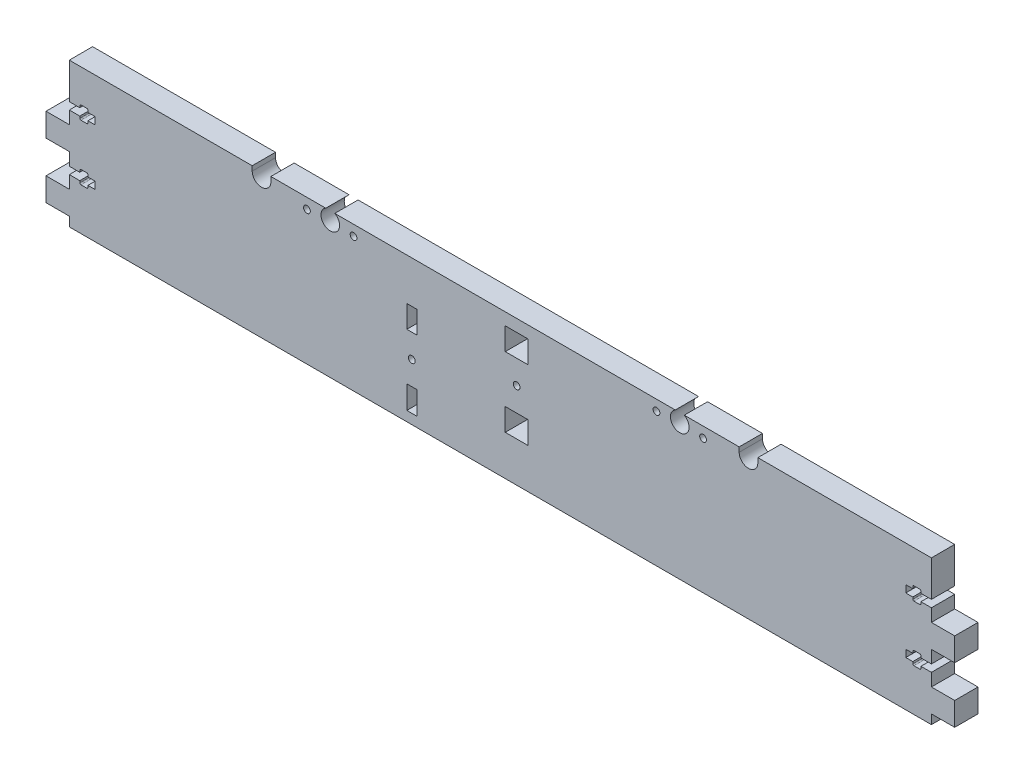
SolidWorks part; units mm, degrees
ref_plane "Front Plane" through (0, 0, 0) normal (0, 0, 1) x (1, 0, 0)
ref_plane "Top Plane" through (0, 0, 0) normal (0, 1, 0) x (1, 0, 0)
ref_plane "Right Plane" through (0, 0, 0) normal (1, 0, 0) x (0, 0, -1)
sketch "Sketch1" plane through (0, 0, 0) normal (0, 0, 1) x (1, 0, 0)
  line L0 (0, 0) -> (-185, 0)
  line L1 (-185, 0) -> (-185, -62) construction
  line L2 (0, -62) -> (-185, -62)
  line L3 (-185, -62) -> (-185, -58)
  line L4 (-185, -58) -> (-195, -58)
  line L5 (-195, -58) -> (-195, -48)
  line L6 (-195, -48) -> (-185, -48)
  line L7 (-185, -48) -> (-185, -34)
  line L8 (-185, -34) -> (-195, -34)
  line L9 (-195, -34) -> (-195, -24)
  line L10 (-195, -24) -> (-185, -24)
  line L11 (0, -62) -> (0, 0)
  line L12 (-185, -24) -> (-185, 0)
  line L13 (-195, -58) -> (-195, -24) construction
  line L14 (-195, -29) -> (-185, -29) construction
  line L15 (-195, -53) -> (-185, -53) construction
  dimension "D1" = 185
  dimension "D2" = 10
  dimension "D3" = 10
  dimension "D4" = 10
  dimension "D5" = 24
  dimension "D6" = 29
  dimension "D7" = 62
extrude "MainBody" add sketch "Sketch1" along normal blind 10
sketch "Sketch3" plane through (0, 0, 10) normal (0, 0, 1) x (1, 0, 0)
  line L0 (-185, -17) -> (-174, -17) construction
  line L1 (-185, 0) -> (-185, -24) construction
  line L2 (-185, -18.55) -> (-180.5, -18.55)
  line L3 (-180.5, -18.55) -> (-180.5, -19.35)
  line L4 (-180, -19.85) -> (-177.5, -19.85)
  line L5 (-177, -19.35) -> (-177, -18.55)
  line L6 (-177, -18.55) -> (-174, -18.55)
  line L7 (-174, -18.55) -> (-174, -15.45)
  line L8 (-180.5, -18.55) -> (-177, -18.55) construction
  line L9 (-195, -24) -> (-195, -34) construction
  line L10 (-180.5, -15.45) -> (-177, -15.45) construction
  line L11 (-177, -15.45) -> (-174, -15.45)
  line L12 (-177, -14.65) -> (-177, -15.45)
  line L13 (-180, -14.15) -> (-177.5, -14.15)
  line L14 (-180.5, -15.45) -> (-180.5, -14.65)
  line L15 (-185, -15.45) -> (-180.5, -15.45)
  line L16 (-185, -18.55) -> (-185, -15.45)
  line L17 (-185, -24) -> (-185, -34) construction
  line L19 (-195, -24) -> (-195, -34) construction
  line L20 (-195, -29) -> (-185, -29) construction
  line L21 (-180.5, -42.55) -> (-177, -42.55) construction
  line L22 (-180.5, -39.45) -> (-177, -39.45) construction
  line L23 (-185, -41) -> (-174, -41) construction
  line L24 (-185, -39.45) -> (-185, -42.55)
  line L25 (-185, -42.55) -> (-180.5, -42.55)
  line L26 (-180.5, -42.55) -> (-180.5, -43.35)
  line L27 (-180, -43.85) -> (-177.5, -43.85)
  line L28 (-177, -43.35) -> (-177, -42.55)
  line L29 (-177, -42.55) -> (-174, -42.55)
  line L30 (-174, -39.45) -> (-174, -42.55)
  line L31 (-177, -39.45) -> (-174, -39.45)
  line L32 (-177, -38.65) -> (-177, -39.45)
  line L33 (-180, -38.15) -> (-177.5, -38.15)
  line L34 (-180.5, -39.45) -> (-180.5, -38.65)
  line L35 (-185, -39.45) -> (-180.5, -39.45)
  line L36 (-180.5, -15.45) -> (-177, -15.45) construction
  arc A0 (-177.5, -19.85) -> (-177, -19.35) centre (-177.5, -19.35) ccw
  arc A1 (-180.5, -19.35) -> (-180, -19.85) centre (-180, -19.35) ccw
  arc A2 (-180.5, -14.65) -> (-180, -14.15) centre (-180, -14.65) cw
  arc A3 (-177.5, -14.15) -> (-177, -14.65) centre (-177.5, -14.65) cw
  arc A4 (-177.5, -43.85) -> (-177, -43.35) centre (-177.5, -43.35) ccw
  arc A5 (-180.5, -43.35) -> (-180, -43.85) centre (-180, -43.35) ccw
  arc A6 (-180.5, -38.65) -> (-180, -38.15) centre (-180, -38.65) cw
  arc A7 (-177.5, -38.15) -> (-177, -38.65) centre (-177.5, -38.65) cw
  point P6 (-195, -29)
  point P15 (-177, -19.85)
  point P18 (-180.5, -19.85)
  point P29 (-180.5, -14.15)
  point P30 (-177, -14.15)
  point P62 (-177, -43.85)
  point P63 (-180.5, -43.85)
  point P64 (-180.5, -38.15)
  point P65 (-177, -38.15)
  dimension "D2" = 8
  dimension "D7" = 0.5
  dimension "D1" = 11
  dimension "D3" = 1.55
  dimension "D4" = 2.85
  dimension "D5" = 12
  dimension "D6" = 3.5
extrude "ScrewCutouts" cut sketch "Sketch3" against normal through all
mirror "Mirror1" about plane through (0, 0, 0) normal (1, 0, 0) of "ScrewCutouts", "MainBody"
sketch "Sketch2" plane through (0, 0, 10) normal (0, 0, 1) x (1, 0, 0)
  line L0 (0, 0) -> (0, -62) construction
  line L1 (-185, -62) -> (185, -62) construction
  line L2 (2, 0) -> (2, -62) construction
  line L3 (185, 0) -> (-185, 0) construction
  line L4 (-63, -4.5) -> (-83, -4.5) construction
  line L5 (-73, -7.5) -> (-73, 0.5) construction
  line L6 (77, -7.5) -> (77, 0.5) construction
  line L7 (67, -4.5) -> (87, -4.5) construction
  circle A0 centre (-73, -3.5) radius 4
  circle A1 centre (-83, -4.5) radius 1.45
  circle A2 centre (-63, -4.5) radius 1.45
  circle A3 centre (67, -4.5) radius 1.45
  circle A4 centre (87, -4.5) radius 1.45
  circle A5 centre (77, -3.5) radius 4
  dimension "D1" = 2.9
  dimension "D2" = 8
  dimension "D4" = 3.5
  dimension "D5" = 75
  dimension "D6" = 2
  dimension "D3" = 10
  dimension "D7" = 1
extrude "RodCutouts" cut sketch "Sketch2" against normal through all
sketch "Sketch4" plane through (0, 0, 10) normal (0, 0, 1) x (1, 0, 0)
  line L0 (77, -3.5) -> (-73, -3.5) construction
  line L1 (2, -3.5) -> (2, -62) construction
  line L2 (-185, -62) -> (185, -62) construction
  line L3 (7, -44.8) -> (7, -5.2) construction
  line L4 (75.0635, 0) -> (-71.0635, 0) construction
  line L5 (7, -10) -> (7, -40) construction
  line L6 (2.1, -5.2) -> (11.9, -5.2)
  line L7 (2.1, -5.2) -> (2.1, -14.8)
  line L8 (2.1, -14.8) -> (11.9, -14.8)
  line L9 (11.9, -5.2) -> (11.9, -14.8)
  line L10 (2.1, -5.2) -> (11.9, -14.8) construction
  line L11 (2.1, -14.8) -> (11.9, -5.2) construction
  line L12 (2.1, -35.2) -> (11.9, -35.2)
  line L13 (2.1, -35.2) -> (2.1, -44.8)
  line L14 (2.1, -44.8) -> (11.9, -44.8)
  line L15 (11.9, -35.2) -> (11.9, -44.8)
  line L16 (2.1, -35.2) -> (11.9, -44.8) construction
  line L17 (2.1, -44.8) -> (11.9, -35.2) construction
  circle A0 centre (7, -25) radius 1.45
  point P12 (7, -10)
  point P17 (7, -40)
  dimension "D8" = 2.9
  dimension "D1" = 9.8
  dimension "D2" = 9.6
  dimension "D3" = 9.8
  dimension "D4" = 9.6
  dimension "D5" = 30
  dimension "D6" = 10
  dimension "D7" = 5
extrude "Cut-Extrude3" cut sketch "Sketch4" against normal through all
sketch "Sketch5" plane through (0, 0, 10) normal (0, 0, 1) x (1, 0, 0)
  line L0 (-38, 0) -> (-38, -62) construction
  line L1 (-74.9365, 0) -> (-185, 0) construction
  line L2 (-185, -62) -> (185, -62) construction
  line L3 (-40.15, -27.625) -> (-40.15, -47.875) construction
  line L4 (-40.15, -18.025) -> (-35.85, -18.025)
  line L5 (-40.15, -18.025) -> (-40.15, -27.625)
  line L6 (-40.15, -27.625) -> (-35.85, -27.625)
  line L7 (-35.85, -18.025) -> (-35.85, -27.625)
  line L8 (-40.15, -18.025) -> (-35.85, -27.625) construction
  line L9 (-40.15, -27.625) -> (-35.85, -18.025) construction
  line L10 (-40.15, -47.875) -> (-35.85, -47.875)
  line L11 (-40.15, -47.875) -> (-40.15, -57.775)
  line L12 (-40.15, -57.775) -> (-35.85, -57.775)
  line L13 (-35.85, -47.875) -> (-35.85, -57.775)
  line L14 (-40.15, -47.875) -> (-35.85, -57.775) construction
  line L15 (-40.15, -57.775) -> (-35.85, -47.875) construction
  line L16 (-35.85, -47.875) -> (-35.85, -27.625) construction
  line L17 (-40.15, -37.75) -> (-35.85, -37.75) construction
  line L18 (-73, -3.5) -> (77, -3.5) construction
  line L19 (2, -3.5) -> (2, -62) construction
  line L20 (2, -32.75) -> (-195, -32.75) construction
  line L21 (-195, -24) -> (-195, -34) construction
  line L22 (-31.65, 8.9944) -> (-31.65, 5) construction
  line L23 (75.0635, 0) -> (-71.0635, 0) construction
  line L24 (-28.45, 8.9944) -> (-28.45, 5)
  line L25 (-34.85, 8.9944) -> (-34.85, 5)
  circle A0 centre (-38, -37.75) radius 1.45
  arc A1 (-28.45, 8.9944) -> (-34.85, 8.9944) centre (-31.65, 8.9944) ccw
  arc A2 (-34.85, 5) -> (-28.45, 5) centre (-31.65, 5) ccw
  point P6 (-38, -22.825)
  point P11 (-38, -52.825)
  point P34 (-31.65, 6.9972)
  dimension "D4" = 9.6
  dimension "D5" = 30
  dimension "D6" = 2.9
  dimension "D9" = 3.2
  dimension "D1" = 4.3
  dimension "D2" = 0
  dimension "D3" = 9.9
  dimension "D7" = 40
  dimension "D8" = 5
  dimension "D10" = 5
  dimension "D11" = 1
extrude "EndstopHolder" cut sketch "Sketch5" against normal through all
sketch "Sketch6" plane through (0, 0, 10) normal (0, 0, 1) x (1, 0, 0)
  line L0 (-40.15, -47.875) -> (-40.15, -27.625) construction
  line L1 (-42.35, -47.875) -> (-27.85, -47.875) construction
  line L3 (-27.85, -53.875) -> (-27.85, -41.875) construction
  line L4 (-29.85, -53.875) -> (-29.85, -41.875)
  line L5 (-25.85, -53.875) -> (-25.85, -41.875)
  line L6 (-35.85, -47.875) -> (-40.15, -47.875) construction
  line L7 (-35.85, -57.775) -> (-35.85, -47.875) construction
  arc A0 (-29.85, -53.875) -> (-25.85, -53.875) centre (-27.85, -53.875) ccw
  arc A1 (-25.85, -41.875) -> (-29.85, -41.875) centre (-27.85, -41.875) ccw
  point P10 (-27.85, -47.875)
  dimension "D1" = 2
  dimension "D2" = 12
  dimension "D3" = 8
  dimension "D4" = 0
extrude "EndstopWires" [suppressed] cut sketch "Sketch6" against normal through all
sketch "Sketch7" plane through (0, 0, 10) normal (0, 0, 1) x (1, 0, 0)
  line L0 (-73, -3.5) -> (77, -3.5) construction
  line L1 (2, -3.5) -> (2, -62) construction
  line L3 (-102.5, 0) -> (-102.5, -2) construction
  line L4 (-74.9365, 0) -> (-185, 0) construction
  line L5 (-98.5, 0) -> (-98.5, -2)
  line L6 (-106.5, 0) -> (-106.5, -2)
  line L7 (106.5, 0) -> (106.5, -2) construction
  line L8 (102.5, 0) -> (102.5, -2)
  line L9 (110.5, 0) -> (110.5, -2)
  line L10 (-185, -62) -> (185, -62) construction
  arc A0 (-98.5, 0) -> (-106.5, 0) centre (-102.5, 0) ccw
  arc A1 (-106.5, -2) -> (-98.5, -2) centre (-102.5, -2) ccw
  arc A2 (102.5, 0) -> (110.5, 0) centre (106.5, 0) cw
  arc A3 (110.5, -2) -> (102.5, -2) centre (106.5, -2) cw
  point P12 (-102.5, -1)
  point P19 (106.5, -1)
  dimension "D3" = 4
  dimension "D1" = 2
  dimension "D2" = 104.5
extrude "Cut-Extrude4" cut sketch "Sketch7" against normal through all
equation "\"Y-ROD-SPACING\"=75"
equation "\"D5@Sketch2\"=\"Y-ROD-SPACING\""
equation "\"Y-BED-OFFSET\"=2"
equation "\"D6@Sketch2\"=\"Y-BED-OFFSET\""
equation "\"T-SLOT-NUT-FILLET-RADIUS\"=0.5"
equation "\"D7@Sketch3\"=\"T-SLOT-NUT-FILLET-RADIUS\""
equation "\"T-SLOT-SCREW-SHAFT-RADIUS\"=1.55"
equation "\"D3@Sketch3\"=\"T-SLOT-SCREW-SHAFT-RADIUS\""
equation "\"T-SLOT-SCREW-SHAFT-CUTOUT-LENGTH\"=11"
equation "\"D1@Sketch3\"=\"T-SLOT-SCREW-SHAFT-CUTOUT-LENGTH\""
equation "\"T-SLOT-NUT-DEPTH\"=3.5"
equation "\"D6@Sketch3\"=\"T-SLOT-NUT-DEPTH\""
equation "\"T-SLOT-NUT-WIDTH\"=2.85"
equation "\"D4@Sketch3\"=\"T-SLOT-NUT-WIDTH\""
equation "\"T-SLOT-NUT-END-DISTANCE\"=8"
equation "\"D2@Sketch3\"=\"T-SLOT-NUT-END-DISTANCE\""
equation "\"ACRYLIC-TAB-CUTOUT-SIZE\"=\"ACRYLIC-THICKNESS\"+\"ACRYLIC-TAB-TOLERANCE\"*2"
equation "\"D1@Sketch4\"=\"ACRYLIC-THICKNESS\"-\"KERF\"*2"
equation "\"D2@Sketch4\"=\"ACRYLIC-TAB-WIDTH\"-\"KERF\"*4"
equation "\"D3@Sketch4\"=\"ACRYLIC-THICKNESS\"-\"KERF\"*2"
equation "\"D4@Sketch4\"=\"ACRYLIC-TAB-WIDTH\"-\"KERF\"*4"
equation "\"ACRYLIC-M3-HOLE\"=2.9"
equation "\"D8@Sketch4\"=\"ACRYLIC-M3-HOLE\""
equation "\"Y-BED-ROD-INSET\"=3.5"
equation "\"D1@Sketch2\"=\"ACRYLIC-M3-HOLE\""
equation "\"D4@Sketch2\"=\"Y-BED-ROD-INSET\""
equation "\"SMOOTHROD-CAP-SCREW-DISTANCE\"=20"
equation "\"D3@Sketch2\"=\"SMOOTHROD-CAP-SCREW-DISTANCE\"/2"
equation "\"ACRYLIC-TAB-WIDTH\"=\"ACRYLIC-THICKNESS\""
equation "\"FRAME-WIDTH-INNER\"=370"
equation "\"D2@Sketch1\"=\"ACRYLIC-TAB-WIDTH\""
equation "\"D3@Sketch1\"=\"ACRYLIC-TAB-WIDTH\""
equation "\"D4@Sketch1\"=\"ACRYLIC-TAB-WIDTH\""
equation "\"D1@Sketch1\"=\"FRAME-WIDTH-INNER\"/2"
equation "\"X-ROD-SPACING\"=45"
equation "\"Z-ROD-SPACING\"=17.5"
equation "\"ACRYLIC-THICKNESS\"=10"
equation "\"ACRYLIC-THICKNESS2\"=4.5"
equation "\"NEMA17-HOLE-SPACING\"=31"
equation "\"NEMA17-CENTRAL-CUTOUT\"=22.5"
equation "\"Z-BRACKET-REACH\"=55"
equation "\"TOP-BRACKET-SPACING\"=40"
equation "\"SMOOTHROD-X-LENGTH\"=350"
equation "\"SMOOTHROD-Y-LENGTH\"=350"
equation "\"SMOOTHROD-Z-LENGTH\"=350"
equation "\"SMOOTHROD-TIGHTENING-HEADROOM\"=.25"
equation "\"LEADSCREW-Z-LENGTH\"=300"
equation "\"SCREW-LENGTH-FRAME\"=\"ACRYLIC-THICKNESS\" + 10"
equation "\"SCREW-HEAD-RADIUS\"=6"
equation "\"PRINTED-X-SMOOTHROD-DIAMETER\"=9.0"
equation "\"PRINTED-X-SMOOTHROD-CUTOUT\"=10"
equation "\"PRINTED-X-BASE-HEIGHT\"=10"
equation "\"PRINTED-LM8UU-CUTOUT-SIZE\"=15.5"
equation "\"PRINTED-LM8UU-CUTOUT-LENGTH\"=24.5"
equation "\"PRINTED-X-IDLER-HEIGHT\"=16"
equation "\"PSU-MOUNTING-WIDTH\"=95"
equation "\"PSU-MOUNTING-HEIGHT\"=177"
equation "\"D1@MainBody\"=\"ACRYLIC-THICKNESS\""
equation "\"D1@Sketch5\"=\"ACRYLIC-THICKNESS2\"-\"KERF\"*2"
equation "\"D3@Sketch5\"=\"ACRYLIC-TAB-CUTOUT-SIZE\""
equation "\"D4@Sketch5\"=\"ACRYLIC-TAB-WIDTH\"-\"KERF\"*4"
equation "\"D6@Sketch5\"=\"ACRYLIC-M3-HOLE\""
equation "\"Y-BED-SCREW-SPACING\"=209"
equation "\"Y-BED-SCREW-CUTOUT-SLOT-HEIGHT\"=2"
equation "\"Z-ROD-INSET\"=13.5"
equation "\"Y-BELT-TO-ROD-DISTANCE\"=20"
equation "\"SPOOL-HOLDER-ROD-SPACING\"=150"
equation "\"D1@Sketch7\"=\"Y-BED-SCREW-CUTOUT-SLOT-HEIGHT\""
equation "\"D2@Sketch7\"=\"Y-BED-SCREW-SPACING\"/2"
equation "\"ACRYLIC-TAB-TOLERANCE\"=-.05"
equation "\"SCREW-LENGTH-MOTOR\"=\"ACRYLIC-THICKNESS\" + 5"
equation "\"SCREW-LENGTH-EXTRUDER\"=28"
equation "\"ACRYLIC-X-CARRIAGE-WIDTH\"=55"
equation "\"ACRYLIC-X-CARRIAGE-HEIGHT\"=75"
equation "\"ACRYLIC-X-CARRIAGE-LM8UU-CUTOUT-WIDTH\"=24.25"
equation "\"ACRYLIC-X-CARRIAGE-SCREW-SPACING-X\"=15"
equation "\"ACRYLIC-X-CARRIAGE-SCREW-SPACING-Y\"=33"
equation "\"ACRYLIC-X-CARRIAGE-CENTER-TAB-SPACING\"=14"
equation "\"ACRYLIC-X-CARRIAGE-EXTRUDER-OFFSET\"=26"
equation "\"ACRYLIC-X-CARRIAGE-EXTRUDER-ANGLE\"=90"
equation "\"ACRYLIC-X-CARRIAGE-EXTRUDER-SHELF-DEPTH\"=\"ACRYLIC-X-CARRIAGE-EXTRUDER-OFFSET\" + 28"
equation "\"ACRYLIC-X-CARRIAGE-EXTRUDER-BRACE-SPACING\"=23"
equation "\"ACRYLIC-X-CARRIAGE-EXTRUDER-BRACE-TAB-OFFSET\"=20"
equation "\"ACRYLIC-X-CARRIAGE-EXTRUDER-BRACE-HEIGHT\"=35"
equation "\"ACRYLIC-X-CARRIAGE-EXTRUDER-BRACE-SCREW-SPACING\"=22"
equation "\"PRINTED-M3-HOLE\"=3.5"
equation "\"ACRYLIC-X-CARRIAGE-LM8UU-CUTOUT-HEIGHT\"=11.0"
equation "\"ACRYLIC-X-CARRIAGE-DUAL-WIDTH-MULTIPLIER\"=1.65"
equation "\"ACRYLIC-X-CARRIAGE-DUAL-HOTEND-SPACING\"=42"
equation "\"ACRYLIC-X-CARRIAGE-DUAL-WIDTH\"=75"
equation "\"ACRYLIC-X-CARRIAGE-DUAL-HOTEND-SEPARATION\"=36"
equation "\"ACRYLIC-X-CARRIAGE-DUAL-MOUNT-PLATE-DEPTH\"=75"
equation "\"ACRYLIC-X-CARRIAGE-DUAL-MOUNT-BRACE-WIDTH\"=33"
equation "\"ACRYLIC-X-CARRIAGE-DUAL-MOUNT-SCREW-WIDTH\"=40"
equation "\"BLOWER-FAN-WIDTH\"=15"
equation "\"KERF\"=0.1"
equation "\"PRINTED-M3-NUT-AF\"=6.25"
equation "\"ACRYLIC-X-CARRIAGE-DUAL-FAN-OFFSET\"=52"
equation "\"ACRYLIC-X-CARRIAGE-DUAL-FAN-HEIGHT\"=20"
